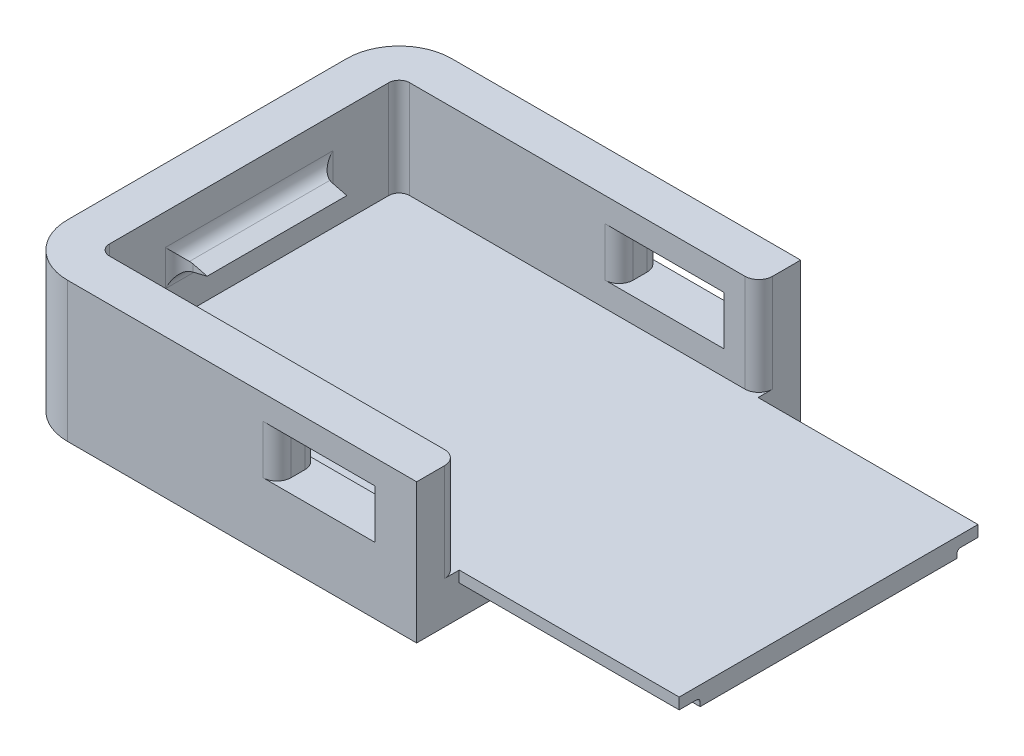
SolidWorks part; units mm, degrees
ref_plane "Alzado" through (0, 0, 0) normal (0, 0, 1) x (1, 0, 0)
ref_plane "Planta" through (0, 0, 0) normal (0, 1, 0) x (1, 0, 0)
ref_plane "Vista lateral" through (0, 0, 0) normal (1, 0, 0) x (0, 0, -1)
sketch "Croquis1" plane through (0, 0, 0) normal (0, 1, 0) x (1, 0, 0)
  line L0 (28.75, 0) -> (-28.75, 0) construction
  line L1 (25, 13.75) -> (-25, 13.75)
  line L2 (25, -13.75) -> (-25, -13.75)
  line L3 (-28.75, 10) -> (-28.75, -10)
  line L4 (28.75, 10) -> (28.75, -10)
  line L5 (0, -13.75) -> (0, 13.75) construction
  arc A0 (28.75, -10) -> (25, -13.75) centre (25, -10) cw
  arc A1 (-25, -13.75) -> (-28.75, -10) centre (-25, -10) cw
  arc A2 (28.75, 10) -> (25, 13.75) centre (25, 10) ccw
  arc A3 (-25, 13.75) -> (-28.75, 10) centre (-25, 10) ccw
  point P3 (0, 0)
  point P18 (0, 0)
  dimension "D1" = 3.75
  dimension "D2" = 57.5
  dimension "D3" = 27.5
  dimension "D4" = 10
extrude "Saliente-Extruir1" add sketch "Croquis1" along normal blind 3
sketch "Croquis2" plane through (0, 0, 0) normal (0, -1, 0) x (1, 0, 0)
  line L0 (25, -13.75) -> (-25, -13.75) construction
  circle A1 centre (0, 0) radius 7.63
  point P3 (0, -13.75)
  dimension "D1" = 15.26
extrude "Saliente-Extruir2" add sketch "Croquis2" along normal blind 3
sketch "Croquis3" plane through (0, 0, 0) normal (0, 0, 1) x (1, 0, 0)
  line L0 (7.63, -1.0671) -> (7.63, -3)
  line L1 (7.73, -1) -> (7.73, -3) construction
  line L2 (7.63, -1.0671) -> (9.73, -1.9262)
  line L3 (7.73, -1) -> (9.93, -1.9) construction
  line L4 (0, -3) -> (7.73, -3) construction
  line L5 (9.93, -1.9) -> (9.93, -3) construction
  line L6 (9.93, -3) -> (7.73, -3) construction
  line L7 (9.73, -3) -> (9.73, -1.9262) construction
  line L8 (7.73, -1.108) -> (9.73, -1.9262) construction
  line L9 (9.73, -1.9262) -> (9.73, -3)
  line L11 (7.73, -1.108) -> (7.73, -3) construction
  line L12 (-7.63, -3) -> (7.63, -3) construction
  line L13 (0, -3) -> (0, 0) construction
  line L14 (7.63, -3) -> (7.63, 0) construction
  line L15 (7.63, -3) -> (9.73, -3)
  dimension "D1" = 2.2
  dimension "D2" = 1.1
  dimension "D3" = 0.2
  dimension "D4" = 0.1
  dimension "D5" = 7.73
  dimension "D6" = 112.249
revolve "Revolución1" add sketch "Croquis3" angle 45 about L13 other way angle 15
sketch "Croquis5" plane through (0, 0, 0) normal (0, 0, 1) x (1, 0, 0)
  line L1 (-7.63, -3) -> (7.37, -3) construction
  line L3 (7.63, -1.0671) -> (7.63, -3) construction
  line L11 (7.73, -1) -> (7.73, -3) construction
  line L12 (-9.73, -1.9262) -> (-9.73, -3)
  line L13 (7.63, -1.0671) -> (9.73, -1.9262) construction
  line L18 (-7.63, -3) -> (-9.73, -3)
  line L19 (7.73, -1) -> (9.93, -1.9) construction
  line L20 (0, -3) -> (7.73, -3) construction
  line L25 (9.93, -1.9) -> (9.93, -3) construction
  line L26 (9.93, -3) -> (7.73, -3) construction
  line L27 (9.73, -3) -> (9.73, -1.9262) construction
  line L28 (7.73, -1.108) -> (9.73, -1.9262) construction
  line L29 (9.73, -1.9262) -> (9.73, -3) construction
  line L30 (7.73, -1.108) -> (7.73, -3) construction
  line L31 (0, -3) -> (0, 0) construction
  line L32 (7.63, -3) -> (9.73, -3) construction
  line L33 (-7.63, -1.0671) -> (-7.63, -3)
  line L34 (-7.63, -1.0671) -> (-9.73, -1.9262)
  dimension "D1" = 2.2
  dimension "D2" = 1.1
  dimension "D3" = 0.2
  dimension "D4" = 112.249
  dimension "D5" = 7.73
  dimension "D6" = 0.1
  dimension "D7" = 1.9329
revolve "Revolución2" add sketch "Croquis5" angle 45 about L31 other way angle 15
sketch "Croquis6" plane through (0, -3, 0) normal (0, -1, 0) x (1, 0, 0)
  line L0 (0, 0) -> (9.5627, -2.5623) construction
  line L1 (0, 0) -> (-9.5627, 2.5623) construction
  circle A2 centre (-9.5627, 2.5623) radius 1
  circle A3 centre (9.5627, -2.5623) radius 1
  dimension "D1" = 2
  dimension "D2" = 15
  dimension "D3" = 9.9
extrude "Cortar-Extruir1" cut sketch "Croquis6" against normal up to next
fillet "Redondeo4" radius 1 14 edges at (9.3985, -2.4631, 2.5183) (9.0986, -2.4631, -3.4481) (9.6036, -2.4631, -1.5631) (6.8801, -2.4631, -6.8801) (5.3952, -2.0336, -5.3952) (7.37, -2.0336, 1.9748) (-7.37, -2.0336, -1.9748) (-9.3985, -2.4631, -2.5183) (-9.6036, -2.4631, 1.5631) (-9.0986, -2.4631, 3.4481) (-5.3952, -2.0336, 5.3952) (-6.8801, -2.4631, 6.8801) (-7.37, -1.0671, 1.9748) (7.37, -1.0671, -1.9748)
sketch "Croquis8" plane through (0, 3, 0) normal (0, 1, 0) x (1, 0, 0)
  line L0 (25, 10.75) -> (-25, 10.75)
  line L1 (-25.75, 10) -> (-25.75, -10)
  line L2 (-25, -10.75) -> (25, -10.75)
  line L3 (25.75, -10) -> (25.75, 10)
  line L4 (28.75, -10) -> (28.75, 10)
  line L5 (25, 13.75) -> (-25, 13.75)
  line L6 (-28.75, 10) -> (-28.75, -10)
  line L7 (-25, -13.75) -> (25, -13.75)
  line L8 (28.75, -10) -> (28.75, 10)
  line L9 (25, 13.75) -> (-25, 13.75)
  line L10 (-28.75, 10) -> (-28.75, -10)
  line L11 (-25, -13.75) -> (25, -13.75)
  arc A0 (-25, 10.75) -> (-25.75, 10) centre (-25, 10) ccw
  arc A1 (-25.75, -10) -> (-25, -10.75) centre (-25, -10) ccw
  arc A2 (25, -10.75) -> (25.75, -10) centre (25, -10) ccw
  arc A3 (25.75, 10) -> (25, 10.75) centre (25, 10) ccw
  arc A4 (25, -13.75) -> (28.75, -10) centre (25, -10) ccw
  arc A5 (28.75, 10) -> (25, 13.75) centre (25, 10) ccw
  arc A6 (-25, 13.75) -> (-28.75, 10) centre (-25, 10) ccw
  arc A7 (-28.75, -10) -> (-25, -13.75) centre (-25, -10) ccw
  arc A8 (25, -13.75) -> (28.75, -10) centre (25, -10) ccw
  arc A9 (28.75, 10) -> (25, 13.75) centre (25, 10) ccw
  arc A10 (-25, 13.75) -> (-28.75, 10) centre (-25, 10) ccw
  arc A11 (-28.75, -10) -> (-25, -13.75) centre (-25, -10) ccw
  dimension "D1" = 0
  dimension "D2" = 3
extrude "Saliente-Extruir3" add sketch "Croquis8" along normal blind 7
fillet "Redondeo10" [suppressed] radius 1
sketch "Croquis11" plane through (0, 0, 0) normal (0, 0, 1) x (1, 0, 0)
  line L0 (0, 10) -> (0, 3)
  line L1 (-25, 10) -> (25, 10) construction
  line L2 (-25, 3) -> (25, 3) construction
  line L3 (0, 3) -> (15.75, 3)
  line L4 (15.75, 3) -> (15.75, 1.65)
  line L5 (15.75, 1.65) -> (0, 1.65)
  line L6 (0, 1.65) -> (0, 0)
  line L7 (0, 0) -> (-9.73, 0)
  line L8 (-25, 0) -> (25, 0) construction
  line L9 (-9.73, 0) -> (-9.73, -3)
  line L10 (-9.73, -3) -> (28.75, -3)
  line L11 (0, 10) -> (28.75, 10)
  line L12 (28.75, 10) -> (28.75, -3)
  dimension "D1" = 1.35
  dimension "D2" = 15.75
extrude "Cortar-Extruir3" cut sketch "Croquis11" against normal through all both and the other way through all
sketch "Croquis12" plane through (15.75, 0, 0) normal (1, 0, 0) x (0, 0, -1)
  line L0 (0, 0) -> (0, 3) construction
  line L1 (10, 3) -> (-10, 3) construction
  line L11 (-13.75, 3) -> (-10.7, 3)
  line L12 (-13.75, 3) -> (-13.75, 1.65)
  line L13 (-13.75, 1.65) -> (-9.2, 1.65)
  line L14 (-10.7, 3) -> (-10.7, 2.2)
  line L16 (-10.7, 2.2) -> (-9.2, 2.2)
  line L19 (-9.2, 2.2) -> (-9.2, 1.65)
  line L20 (13.75, 3) -> (13.75, 1.65)
  line L21 (13.75, 3) -> (10.7, 3)
  line L22 (10.7, 3) -> (10.7, 2.2)
  line L23 (10.7, 2.2) -> (9.2, 2.2)
  line L24 (9.2, 2.2) -> (9.2, 1.65)
  line L25 (13.75, 1.65) -> (9.2, 1.65)
  dimension "D1" = 0.8
  dimension "D2" = 1.5
  dimension "D3" = 1.35
  dimension "D4" = 3.05
extrude "Cortar-Extruir4" cut sketch "Croquis12" against normal up to surface (15.75 mm away) and the other way through all up to face at (0, 6.5, 12.25)
fillet "Redondeo12" radius 0.25 2 edges at (7.875, 2.2, -9.2) (7.875, 2.2, 9.2)
sketch "Croquis13" plane through (0, 0, 13.75) normal (0, 0, 1) x (1, 0, 0)
  line L0 (0, 10) -> (0, 0) construction
  line L1 (-10, 8.25) -> (-3, 8.25)
  line L2 (-10, 8.25) -> (-10, 4.75)
  line L3 (-10, 4.75) -> (-3, 4.75)
  line L4 (-3, 8.25) -> (-3, 4.75)
  line L6 (-25, 10) -> (0, 10) construction
  point P6 (-10, 6.5)
  dimension "D1" = 3.5
  dimension "D2" = 7
  dimension "D3" = 3
  dimension "D4" = 3.5
extrude "Cortar-Extruir5" cut sketch "Croquis13" against normal up to surface (27.5 mm away) up to face at (-12.5, 5, -13.75)
fillet "Redondeo15" radius 1 4 edges at (-10, 6.5, 10.75) (-10, 6.5, -13.75) (-10, 6.5, -10.75) (-10, 6.5, 13.75)
chamfer "Chaflán1" distance 0.5 angle 45 2 edges at (-3, 6.5, 10.75) (-3, 6.5, -10.75)
sketch "Croquis14" plane through (0, 0, 0) normal (0, 0, 1) x (1, 0, 0)
  line L0 (-25.75, 6.5) -> (-23.75, 6.5) construction
  line L3 (-25.75, 10) -> (-25.75, 3) construction
  line L4 (-25.75, 7) -> (-23.75, 6.5)
  line L5 (-25.75, 6) -> (-23.75, 6.5)
  line L6 (-25.75, 7) -> (-25.75, 6)
  dimension "D1" = 2
  dimension "D2" = 1
extrude "Saliente-Extruir4" add sketch "Croquis14" against normal blind 5 and the other way blind 5
fillet "Redondeo16" radius 1 4 edges at (-25.75, 6.5, 5) (-25.75, 6.5, -5) (-25.75, 6, 0) (-25.75, 7, 0)
fillet "Redondeo18" radius 1 2 edges at (0, 6.5, 10.75) (0, 6.5, -10.75)
